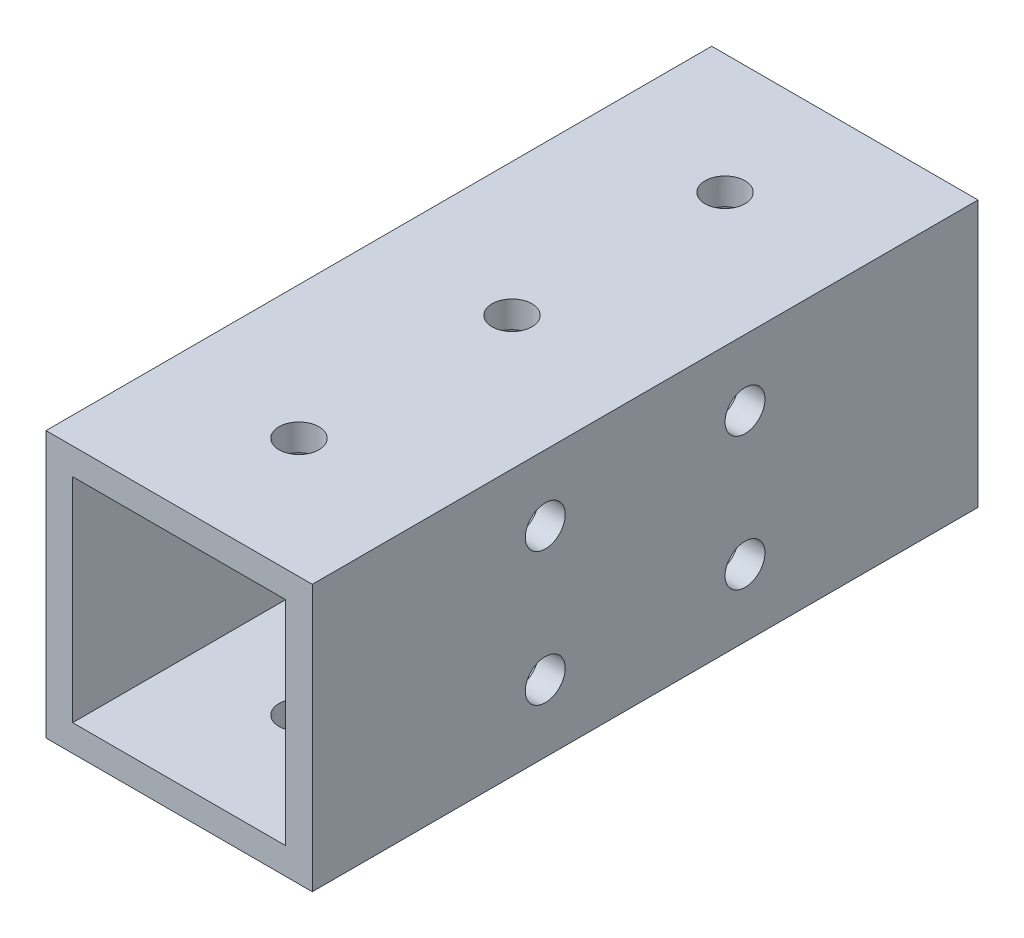
SolidWorks part; units mm, degrees
ref_plane "前视基准面" through (0, 0, 0) normal (0, 0, 1) x (1, 0, 0)
ref_plane "上视基准面" through (0, 0, 0) normal (0, 1, 0) x (1, 0, 0)
ref_plane "右视基准面" through (0, 0, 0) normal (1, 0, 0) x (0, 0, -1)
other "Configuration Table"
sketch "草图1" plane through (0, 0, 0) normal (0, 0, 1) x (1, 0, 0)
  line L1 (-8, -8) -> (8, -8)
  line L2 (-8, -8) -> (-8, 8)
  line L3 (-8, 8) -> (8, 8)
  line L4 (8, -8) -> (8, 8)
  line L5 (-8, -8) -> (8, 8) construction
  line L6 (-8, 8) -> (8, -8) construction
  line L7 (-10, -10) -> (10, -10)
  line L8 (-10, -10) -> (-10, 10)
  line L9 (-10, 10) -> (10, 10)
  line L10 (10, -10) -> (10, 10)
  line L11 (-10, -10) -> (10, 10) construction
  line L12 (-10, 10) -> (10, -10) construction
  point P0 (0, 0)
  point P6 (0, 0)
  dimension "D1" = 20
  dimension "D2" = 20
  dimension "D3" = 2
  dimension "D4" = 2
extrude "凸台-拉伸1" add sketch "草图1" along normal blind 50
sketch "草图2" plane through (10, 0, 0) normal (1, 0, 0) x (0, 0, -1)
  line L0 (-25, 10) -> (-25, -10) construction
  line L1 (-50, 10) -> (0, 10) construction
  line L2 (-50, -10) -> (0, -10) construction
  circle A0 centre (-32.5, 5.05) radius 1.5
  circle A1 centre (-17.5, 5.05) radius 1.5
  circle A2 centre (-32.5, -4.95) radius 1.5
  circle A3 centre (-17.5, -4.95) radius 1.5
  dimension "D1" = 10
  dimension "D2" = 15
  dimension "D4" = 3
  dimension "D3" = 4.95
extrude "切除-拉伸1" cut sketch "草图2" against normal up to surface (20 mm away) up to face at (-10, 0, 25)
sketch "草图3" plane through (0, 10, 0) normal (0, 1, 0) x (1, 0, 0)
  line L0 (0, 0) -> (0, -50) construction
  line L1 (10, -50) -> (-10, -50) construction
  circle A0 centre (0, -25) radius 1.5
  circle A1 centre (0, -9) radius 1.5
  circle A2 centre (0, -41) radius 1.5
  dimension "D1" = 3
  dimension "D2" = 16
  dimension "D3" = 16
extrude "切除-拉伸2" cut sketch "草图3" against normal up to surface (20 mm away) up to face at (0, -10, 25)
